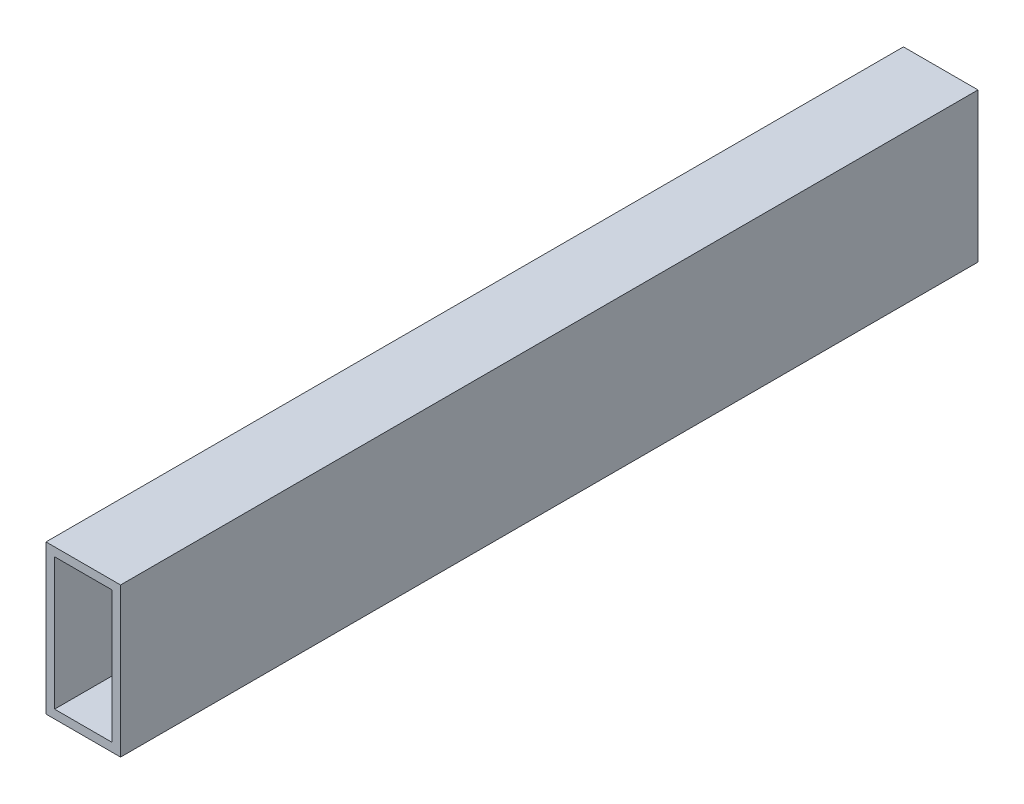
SolidWorks part; units mm, degrees
material "6061 Alloy"
ref_plane "Front Plane" through (0, 0, 0) normal (0, 0, 1) x (1, 0, 0)
ref_plane "Top Plane" through (0, 0, 0) normal (0, 1, 0) x (1, 0, 0)
ref_plane "Right Plane" through (0, 0, 0) normal (1, 0, 0) x (0, 0, -1)
sketch "Sketch1" plane through (0, 0, 0) normal (0, 0, 1) x (1, 0, 0)
  line L0 (-9.779, 22.479) -> (9.779, 22.479)
  line L1 (-12.7, -25.4) -> (12.7, -25.4)
  line L2 (-12.7, -25.4) -> (-12.7, 25.4)
  line L3 (-12.7, 25.4) -> (12.7, 25.4)
  line L4 (12.7, -25.4) -> (12.7, 25.4)
  line L5 (-12.7, -25.4) -> (12.7, 25.4) construction
  line L6 (-12.7, 25.4) -> (12.7, -25.4) construction
  line L7 (9.779, -22.479) -> (9.779, 22.479)
  line L8 (-9.779, -22.479) -> (9.779, -22.479)
  line L9 (-9.779, -22.479) -> (-9.779, 22.479)
  point P0 (0, 0)
  dimension "D1" = 25.4
  dimension "D2" = 50.8
  dimension "D3" = 2.921
extrude "Boss-Extrude1" add sketch "Sketch1" along normal blind 292.1
equation "\"length\"= 11.5"
equation "\"D1@Boss-Extrude1\"=\"length\""
